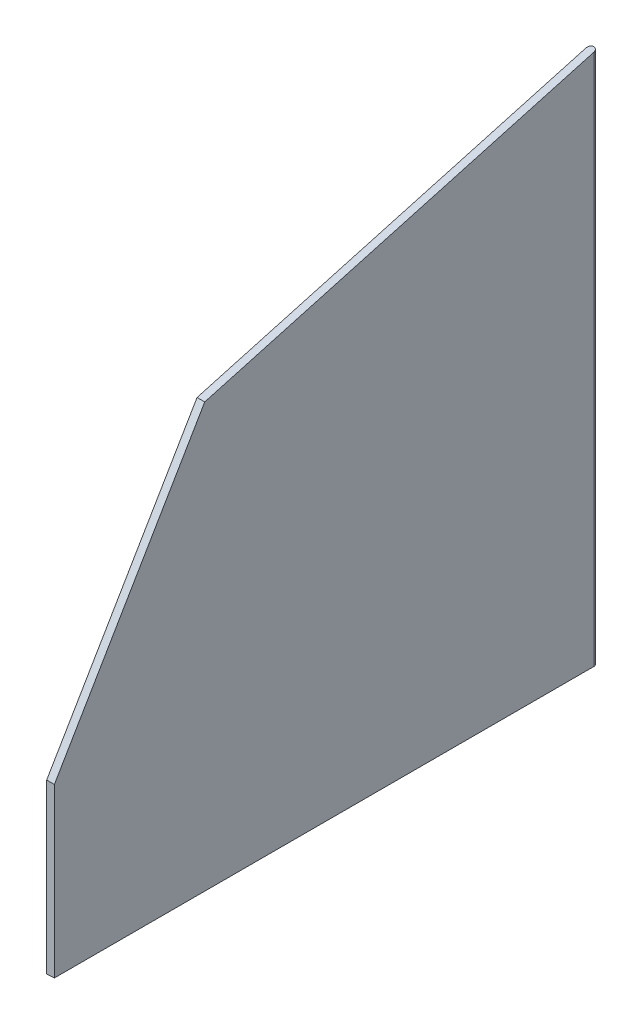
SolidWorks part; units mm, degrees
material "Verre"
ref_plane "Plan de face" through (0, 0, 0) normal (0, 0, 1) x (1, 0, 0)
ref_plane "Plan de dessus" through (0, 0, 0) normal (0, 1, 0) x (1, 0, 0)
ref_plane "Plan de droite" through (0, 0, 0) normal (1, 0, 0) x (0, 0, -1)
sketch "Esquisse1" plane through (0, 0, 0) normal (1, 0, 0) x (0, 0, -1)
  line L0 (635.7096, 813.7456) -> (-385.4717, 529.5119)
  line L1 (-385.4717, 529.5119) -> (-776.2904, -136.2544)
  line L2 (-776.2904, -136.2544) -> (-776.2904, -573.2544)
  line L3 (-776.2904, -573.2544) -> (635.7096, -573.2544)
  line L4 (635.7096, -573.2544) -> (635.7096, 813.7456)
  dimension "D1" = 1387
  dimension "D2" = 1412
  dimension "D3" = 437
  dimension "D4" = 772
  dimension "D5" = 1060
extrude "Boss.-Extru.1" add sketch "Esquisse1" along normal blind 20
sketch "Esquisse4" plane through (0, 0, 0) normal (0, 0, 1) x (1, 0, 0)
  line L3 (20, -573.2544) -> (0, -573.2544)
  line L4 (20, -573.2544) -> (20, -571.9225)
  line L5 (20, -136.2544) -> (20, -573.2544) construction
  line L6 (20, -571.9225) -> (0, -573.2544)
  dimension "D1" = 3.81
extrude "Enlèv. mat.-Extru.1" cut sketch "Esquisse4" against normal blind 792 and the other way blind 871
sketch "Esquisse5" plane through (-37.9191, -575.7796, 0) normal (0.0664, -0.9978, 0) x (0.9978, 0.0664, 0)
  line L2 (38.0031, -635.7096) -> (58.0474, -635.7096) construction
  line L3 (58.0474, 776.2904) -> (58.0474, -635.7096) construction
  circle A0 centre (48.0274, -625.7096) radius 5
  dimension "D1" = 10
  dimension "D2" = 10.02
extrude "Enlèv. mat.-Extru.2" cut sketch "Esquisse5" against normal blind 20
fillet "Congé1" radius 10 2 edges at (20, 120.9115, -635.7096) (0, 120.2456, -635.7096)
